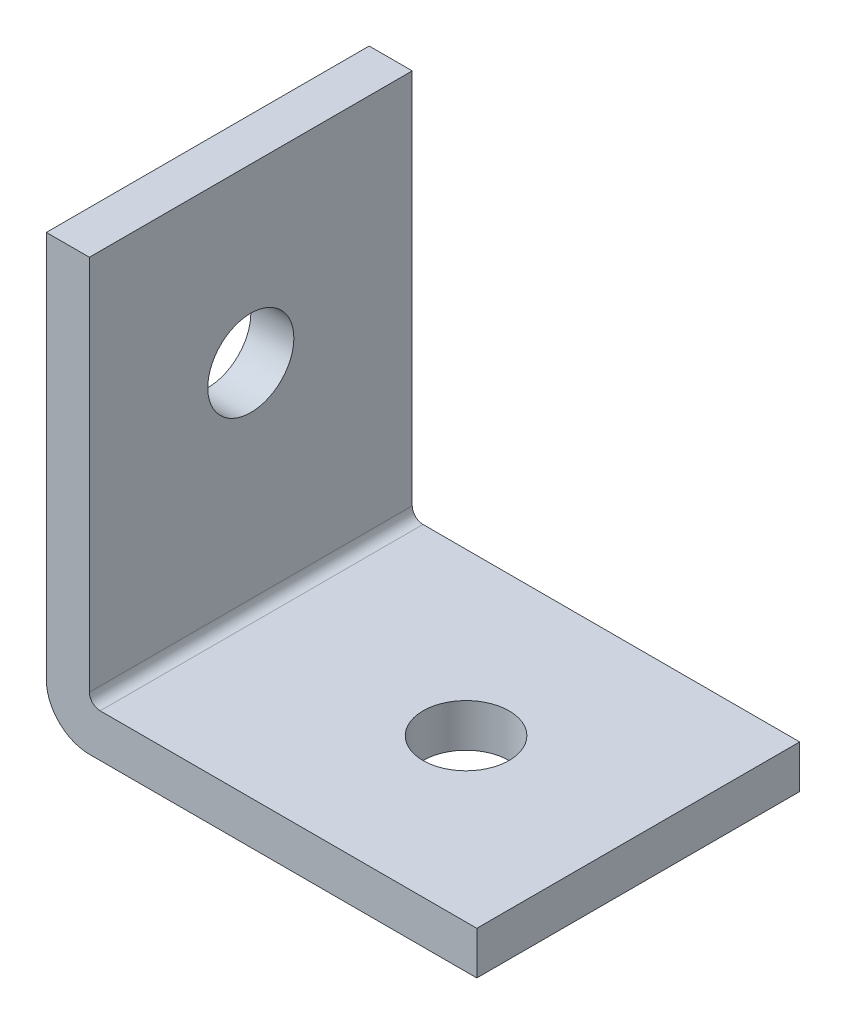
SolidWorks part; units mm, degrees
ref_plane "Front" through (0, 0, 0) normal (0, 0, 1) x (1, 0, 0)
ref_plane "Top" through (0, 0, 0) normal (0, 1, 0) x (1, 0, 0)
ref_plane "Right" through (0, 0, 0) normal (1, 0, 0) x (0, 0, -1)
sketch "Sketch1" plane through (0, 0, 0) normal (0, 0, 1) x (1, 0, 0)
  line L0 (0, 2) -> (0, 20)
  line L1 (0, 20) -> (2, 20)
  line L2 (2, 20) -> (2, 2.5)
  line L3 (2.5, 2) -> (20, 2)
  line L4 (20, 2) -> (20, 0)
  line L5 (20, 0) -> (2, 0)
  arc A0 (0, 2) -> (2, 0) centre (2, 2) ccw
  arc A1 (2.5, 2) -> (2, 2.5) centre (2.5, 2.5) cw
  point P9 (0, 0)
  point P12 (2, 2)
  dimension "D5" = 2
  dimension "D6" = 0.5
  dimension "D1" = 2
  dimension "D2" = 2
  dimension "D3" = 18
  dimension "D4" = 18
extrude "Boss-Extrude1" add sketch "Sketch1" along normal blind 15
ref_plane "Plane1" through (2, 0, 0) normal (1, 0, 0) x (0, 0, -1)
ref_plane "Plane2" through (0, 2, 0) normal (0, 1, 0) x (1, 0, 0)
sketch "Sketch3" plane through (0, 2, 0) normal (0, 1, 0) x (1, 0, 0)
  line L0 (20, 0) -> (2.5, 0) construction
  line L1 (20, -15) -> (20, 0) construction
  circle A0 centre (12, -7.5) radius 2
  dimension "D1" = 4
  dimension "D2" = 7.5
  dimension "D3" = 8
extrude "Cut-Extrude2" cut sketch "Sketch3" against normal through all contours A0
sketch "Sketch4" plane through (2, 0, 0) normal (1, 0, 0) x (0, 0, -1)
  line L0 (-15, 2.5) -> (-15, 20) construction
  line L2 (-15, 20) -> (0, 20) construction
  circle A0 centre (-7.5, 12) radius 2
  dimension "D1" = 4
  dimension "D2" = 7.5
  dimension "D3" = 8
extrude "Cut-Extrude3" cut sketch "Sketch4" against normal through all contours A0
